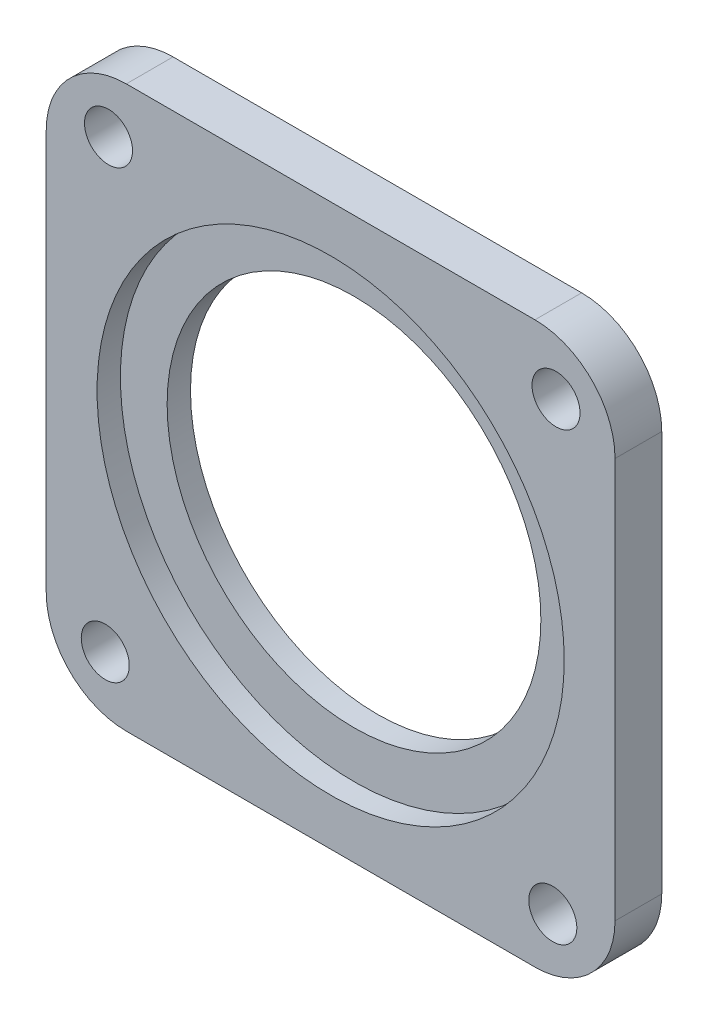
SolidWorks part; units mm, degrees
ref_plane "Płaszczyzna przednia" through (0, 0, 0) normal (0, 0, 1) x (1, 0, 0)
ref_plane "Płaszczyzna górna" through (0, 0, 0) normal (0, 1, 0) x (1, 0, 0)
ref_plane "Płaszczyzna prawa" through (0, 0, 0) normal (1, 0, 0) x (0, 0, -1)
sketch "Sketch1" plane through (0, 0, 0) normal (0, 0, 1) x (1, 0, 0)
  line L1 (21.3073, -21) -> (-21.3073, -21)
  line L2 (21.3073, -21) -> (21.3073, 21)
  line L3 (21.3073, 21) -> (-21.3073, 21)
  line L4 (-21.3073, -21) -> (-21.3073, 21)
  line L5 (21.3073, -21) -> (-21.3073, 21) construction
  line L6 (21.3073, 21) -> (-21.3073, -21) construction
  circle A0 centre (0, 0) radius 21 construction
  circle A1 centre (0, 0) radius 14
  dimension "D1" = 42
  dimension "D2" = 28
extrude "Boss-Extrude1" add sketch "Sketch1" along normal blind 3.5
sketch "Sketch2" plane through (0, 0, 3.5) normal (0, 0, 1) x (1, 0, 0)
  circle A0 centre (0, 0) radius 17.5
  dimension "D2" = 35
extrude "Cut-Extrude1" cut sketch "Sketch2" against normal blind 1.75
hole_wizard "M3 Clearance Hole1" positions "Sketch3" profile "Sketch4" hole size "M3" standard "DIN" end condition through all
sketch "Sketch3" plane through (0, 0, 0) normal (0, 0, -1) x (-1, 0, 0)
  line L0 (-21.3073, 21) -> (-12.4639, 12.2842) construction
  circle A0 centre (0, 0) radius 17.5 construction
  circle A1 centre (0, 0) radius 17.5
  point P9 (-16.8856, 16.6421)
  point P17 (16.6421, 16.8856)
  point P18 (16.8856, -16.6421)
  point P19 (-16.6421, -16.8856)
  dimension "D1" = 4
sketch "Sketch4" plane through (16.6421, -16.8856, 0) normal (1, 0, 0) x (0, 1, 0)
  line L0 (0, 0) -> (0, 3.5)
  line L1 (0, 3.5) -> (1.8, 3.5)
  line L2 (1.8, 3.5) -> (1.8, 0)
  line L5 (1.8, 0) -> (0, 0)
  line L11 (0, -6.35) -> (0, 107.95) construction
  dimension "Thru Hole Dia." = 3.6
  dimension "Thru Hole Depth" = 3.5
fillet "Fillet1" radius 6 4 edges at (-21.3073, 21, 1.75) (-21.3073, -21, 1.75) (21.3073, -21, 1.75) (21.3073, 21, 1.75)
